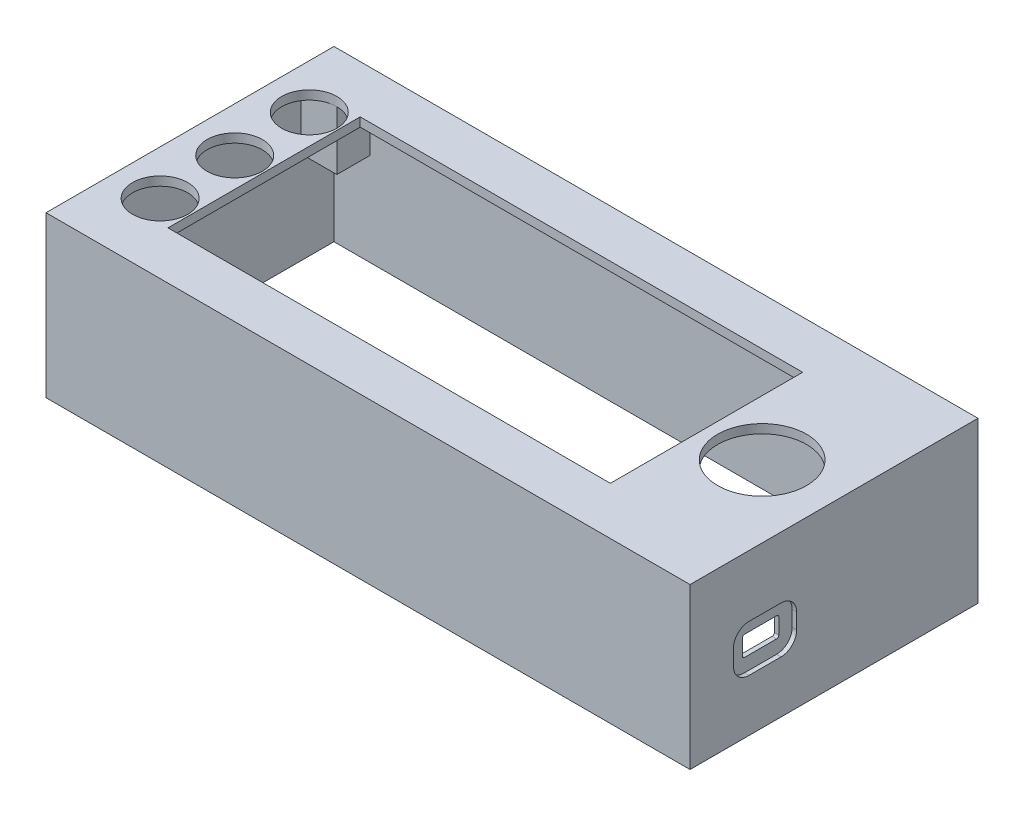
SolidWorks part; units mm, degrees
ref_plane "Спереди" through (0, 0, 0) normal (0, 0, 1) x (1, 0, 0)
ref_plane "Сверху" through (0, 0, 0) normal (0, 1, 0) x (1, 0, 0)
ref_plane "Справа" through (0, 0, 0) normal (1, 0, 0) x (0, 0, -1)
sketch "Эскиз1" plane through (0, 0, 0) normal (0, 1, 0) x (1, 0, 0)
  line L1 (-72.35, 32.35) -> (72.35, 32.35)
  line L2 (-72.35, 32.35) -> (-72.35, -32.35)
  line L3 (-72.35, -32.35) -> (72.35, -32.35)
  line L4 (72.35, 32.35) -> (72.35, -32.35)
  line L5 (-72.35, 32.35) -> (72.35, -32.35) construction
  line L6 (-72.35, -32.35) -> (72.35, 32.35) construction
  point P0 (0, 0)
  dimension "D1" = 144.7
  dimension "D2" = 64.7
extrude "Бобышка-Вытянуть1" add sketch "Эскиз1" along normal blind 36
sketch "Эскиз2" plane through (0, 0, 0) normal (0, -1, 0) x (1, 0, 0)
  line L1 (-70.35, 30.35) -> (70.35, 30.35)
  line L2 (-70.35, 30.35) -> (-70.35, -30.35)
  line L3 (-70.35, -30.35) -> (70.35, -30.35)
  line L4 (70.35, 30.35) -> (70.35, -30.35)
  line L5 (-70.35, 30.35) -> (70.35, -30.35) construction
  line L6 (-70.35, -30.35) -> (70.35, 30.35) construction
  point P0 (0, 0)
  dimension "D1" = 140.7
  dimension "D2" = 60.7
extrude "Вырез-Вытянуть1" cut sketch "Эскиз2" against normal offset from surface (34 mm away) 2 up to face at (0, 36, 0)
sketch "Эскиз3" plane through (0, 36, 0) normal (0, 1, 0) x (1, 0, 0)
  line L0 (42, 19.9) -> (-54, 19.9) construction
  line L1 (-55.7, 21.6) -> (43.7, 21.6)
  line L2 (-55.7, 21.6) -> (-55.7, -21.6)
  line L3 (-55.7, -21.6) -> (43.7, -21.6)
  line L4 (43.7, 21.6) -> (43.7, -21.6)
  line L5 (42, -19.9) -> (42, 19.9) construction
  line L6 (-54, -19.9) -> (42, -19.9) construction
  line L7 (-54, 19.9) -> (-54, -19.9) construction
  dimension "D1" = 1.7
  dimension "D2" = 1.7
  dimension "D3" = 1.7
  dimension "D4" = 1.7
extrude "Вырез-Вытянуть2" cut sketch "Эскиз3" against normal up to surface (2 mm away) up to face at (0, 34, 0)
sketch "Эскиз4" plane through (0, 36, 0) normal (0, 1, 0) x (1, 0, 0)
  circle A0 centre (-62.3, 16.75) radius 6.2
  circle A1 centre (-62.3, 0) radius 6.2
  circle A2 centre (-62.3, -16.75) radius 6.2
  dimension "D1" = 12.4
extrude "Вырез-Вытянуть3" cut sketch "Эскиз4" against normal up to surface (2 mm away) up to face at (-6, 34, 0)
sketch "Эскиз5" plane through (0, 36, 0) normal (0, 1, 0) x (1, 0, 0)
  circle A0 centre (56.2, 0) radius 10
  dimension "D1" = 20
extrude "Вырез-Вытянуть4" cut sketch "Эскиз5" against normal up to surface (2 mm away) up to face at (-62.3, 34, 6.2)
sketch "Эскиз6" plane through (72.35, 0, 0) normal (1, 0, 0) x (0, 0, -1)
  line L0 (-19.2, 16.9) -> (-19.2, 15.3) construction
  line L1 (-11.9, 14.7) -> (-19.1, 14.7)
  line L2 (-11.4, 15.2) -> (-11.4, 18.7)
  line L3 (-11.9, 19.2) -> (-19.1, 19.2)
  line L4 (-19.6, 15.2) -> (-19.6, 18.7)
  line L5 (-12, 15.1) -> (-19, 15.1) construction
  line L6 (-18.5, 18.8) -> (-12.5, 18.8) construction
  line L7 (-11.8, 16.9) -> (-11.8, 15.3) construction
  arc A0 (-11.4, 18.7) -> (-11.9, 19.2) centre (-11.9, 18.7) ccw
  arc A1 (-11.9, 14.7) -> (-11.4, 15.2) centre (-11.9, 15.2) ccw
  arc A2 (-19.1, 14.7) -> (-19.6, 15.2) centre (-19.1, 15.2) cw
  arc A3 (-19.1, 19.2) -> (-19.6, 18.7) centre (-19.1, 18.7) ccw
  dimension "D5" = 0.5
  dimension "D1" = 0.4
  dimension "D2" = 0.4
  dimension "D3" = 0.4
  dimension "D4" = 0.4
extrude "Вырез-Вытянуть5" cut sketch "Эскиз6" against normal up to surface (2 mm away) up to face at (70.35, 17, 0)
sketch "Эскиз7" plane through (72.35, 0, 0) normal (1, 0, 0) x (0, 0, -1)
  line L4 (-11.9, 19.2) -> (-19.1, 19.2) construction
  line L5 (-11.4, 15.2) -> (-11.4, 18.7) construction
  line L6 (-19.1, 14.7) -> (-11.9, 14.7) construction
  line L7 (-19.6, 18.7) -> (-19.6, 15.2) construction
  line L8 (-19.6, 18.7) -> (-19.6, 15.2) construction
  line L9 (-19.1, 14.7) -> (-11.9, 14.7) construction
  line L10 (-11.4, 15.2) -> (-11.4, 18.7) construction
  line L11 (-11.9, 19.2) -> (-19.1, 19.2) construction
  line L12 (-22.6, 18.7) -> (-22.6, 15.2)
  line L13 (-19.1, 11.7) -> (-11.9, 11.7)
  line L14 (-8.4, 15.2) -> (-8.4, 18.7)
  line L15 (-11.9, 22.2) -> (-19.1, 22.2)
  arc A0 (-11.4, 18.7) -> (-11.9, 19.2) centre (-11.9, 18.7) ccw construction
  arc A3 (-11.9, 14.7) -> (-11.4, 15.2) centre (-11.9, 15.2) ccw construction
  arc A4 (-19.6, 15.2) -> (-19.1, 14.7) centre (-19.1, 15.2) ccw construction
  arc A5 (-19.1, 19.2) -> (-19.6, 18.7) centre (-19.1, 18.7) ccw construction
  arc A6 (-19.1, 19.2) -> (-19.6, 18.7) centre (-19.1, 18.7) ccw construction
  arc A7 (-19.6, 15.2) -> (-19.1, 14.7) centre (-19.1, 15.2) ccw construction
  arc A8 (-11.9, 14.7) -> (-11.4, 15.2) centre (-11.9, 15.2) ccw construction
  arc A9 (-11.4, 18.7) -> (-11.9, 19.2) centre (-11.9, 18.7) ccw construction
  arc A10 (-22.6, 15.2) -> (-19.1, 11.7) centre (-19.1, 15.2) ccw
  arc A11 (-11.9, 11.7) -> (-8.4, 15.2) centre (-11.9, 15.2) ccw
  arc A12 (-8.4, 18.7) -> (-11.9, 22.2) centre (-11.9, 18.7) ccw
  arc A13 (-19.1, 22.2) -> (-22.6, 18.7) centre (-19.1, 18.7) ccw
  dimension "D1" = 3
extrude "Вырез-Вытянуть6" cut sketch "Эскиз7" against normal blind 1
sketch "Эскиз8" plane through (0, 34, 0) normal (0, -1, 0) x (1, 0, 0)
  circle A0 centre (-66, 26) radius 1.5
  circle A1 centre (-66, -26) radius 1.5
  circle A2 centre (66, 26) radius 1.5
  circle A3 centre (66, -26) radius 1.5
sketch "Эскиз9" plane through (0, 34, 0) normal (0, -1, 0) x (1, 0, 0)
  line L1 (-70.35, 30.35) -> (-62.3, 30.35)
  line L2 (-70.35, 30.35) -> (-70.35, 22.95)
  line L3 (-70.35, 22.95) -> (-62.3, 22.95)
  line L4 (-62.3, 30.35) -> (-62.3, 22.95)
  line L5 (-70.35, -30.35) -> (-62.3, -30.35)
  line L6 (-70.35, -30.35) -> (-70.35, -22.95)
  line L7 (-70.35, -22.95) -> (-62.3, -22.95)
  line L8 (-62.3, -30.35) -> (-62.3, -22.95)
  line L9 (70.35, 30.35) -> (62.3, 30.35)
  line L10 (70.35, 30.35) -> (70.35, 22.95)
  line L11 (70.35, 22.95) -> (62.3, 22.95)
  line L12 (62.3, 30.35) -> (62.3, 22.95)
  line L13 (70.35, -30.35) -> (62.3, -30.35)
  line L14 (70.35, -30.35) -> (70.35, -22.95)
  line L15 (70.35, -22.95) -> (62.3, -22.95)
  line L16 (62.3, -30.35) -> (62.3, -22.95)
  circle A0 centre (-62.3, 16.75) radius 6.2 construction
  circle A1 centre (-62.3, -16.75) radius 6.2 construction
  dimension "D1" = 8.05
  dimension "D2" = 8.05
extrude "Бобышка-Вытянуть2" add sketch "Эскиз9" along normal blind 13.2
sketch "Эскиз10" plane through (0, 20.8, 0) normal (0, -1, 0) x (1, 0, 0)
  circle A0 centre (66, 26) radius 1.5 construction
  circle A1 centre (66, -26) radius 1.5 construction
  circle A2 centre (-66, -26) radius 1.5 construction
  circle A3 centre (-66, 26) radius 1.5 construction
  circle A4 centre (66, 26) radius 1.5
  circle A5 centre (66, -26) radius 1.5
  circle A6 centre (-66, -26) radius 1.5
  circle A7 centre (-66, 26) radius 1.5
  circle A8 centre (-66, 26) radius 1
  circle A9 centre (-66, -26) radius 1
  circle A10 centre (66, -26) radius 1
  circle A11 centre (66, 26) radius 1
  dimension "D1" = 0.5
extrude "Вырез-Вытянуть7" cut sketch "Эскиз10" against normal up to surface (13.2 mm away) contours A8 | A9 | A10 | A11 region at (-66, 20.8, 26) region at (-66, 20.8, -26) region at (66, 20.8, -26) region at (66, 20.8, 26) up to face at (56.2, 34, 10)
sketch "Эскиз11" plane through (-72.35, 0, 0) normal (-1, 0, 0) x (0, 0, 1)
  line L1 (32.35, 36) -> (2.35, 36)
  line L2 (32.35, 36) -> (32.35, 26)
  line L3 (32.35, 26) -> (2.35, 26)
  line L4 (-32.35, 0) -> (32.35, 0)
  line L5 (32.35, 0) -> (32.35, 36)
  line L6 (32.35, 36) -> (-32.35, 36)
  line L7 (-32.35, 36) -> (-32.35, 0)
  line L8 (-32.35, 0) -> (32.35, 0)
  line L9 (32.35, 0) -> (32.35, 36)
  line L10 (32.35, 36) -> (-32.35, 36)
  line L11 (-32.35, 36) -> (-32.35, 0)
  line L12 (2.35, 36) -> (2.35, 26)
  dimension "D2" = 10
  dimension "D3" = 30
  dimension "D1" = 0
